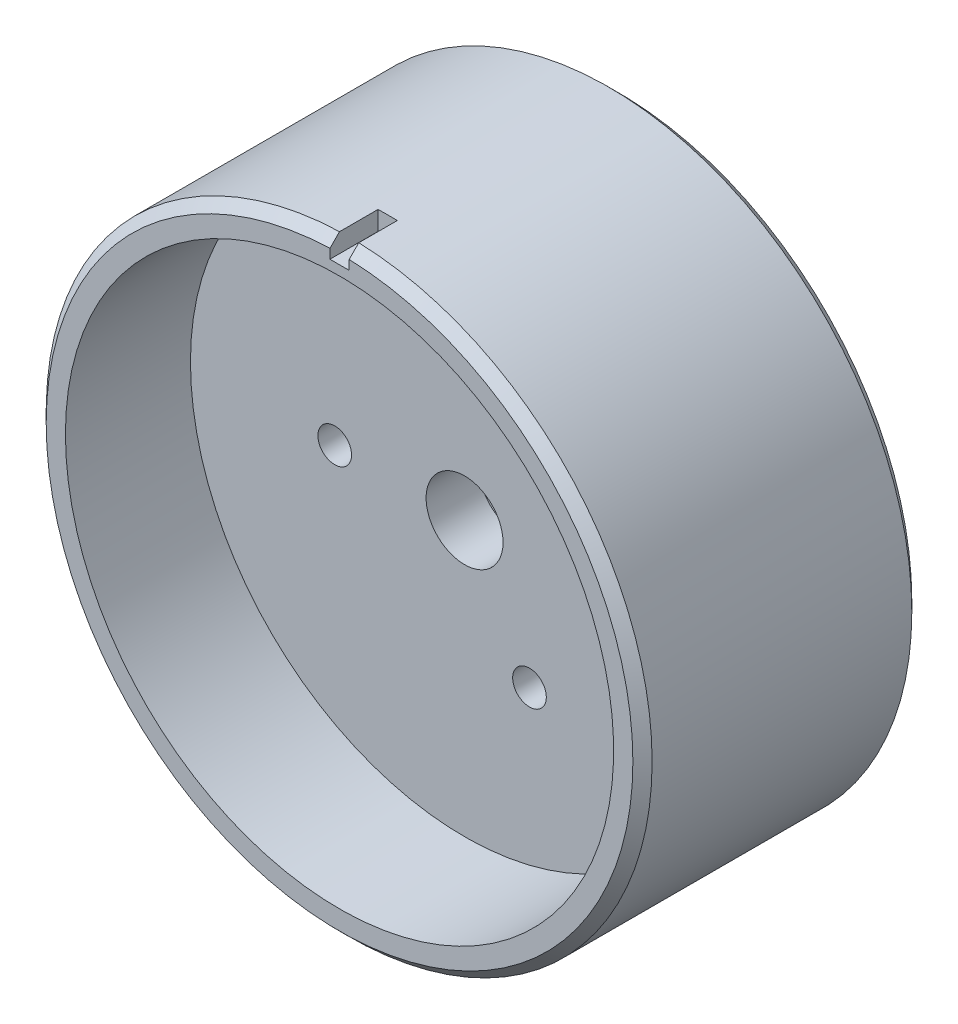
SolidWorks part; units mm, degrees
note: The reader was unsure of these and kept them because the rebuilt part matched: thickness of "Базовая кромка1", "Листовой металл4", "Листовой металл5", "Листовой металл6", "Листовой металл9", "Листовой металл10", "Листовой металл12", "Листовой металл13", "Листовой металл14", "Листовой металл15", "Листовой металл16", "Листовой металл17", "Листовой металл18".
material "PETG"
ref_plane "Спереди" through (0, 0, 0) normal (0, 0, 1) x (1, 0, 0)
ref_plane "Сверху" through (0, 0, 0) normal (0, 1, 0) x (1, 0, 0)
ref_plane "Справа" through (0, 0, 0) normal (1, 0, 0) x (0, 0, -1)
sketch "Эскиз1" plane through (0, 0, 0) normal (0, 0, 1) x (1, 0, 0)
  line L0 (0, 0) -> (-10.2, 0) construction
  line L1 (0, 0) -> (5.1, 8.8335) construction
  line L2 (0, 0) -> (5.1, -8.8335) construction
  line L3 (0, 0) -> (-25, 0) construction
  line L5 (0, 0) -> (0, 25) construction
  circle A0 centre (0, 0) radius 31.5
  circle A1 centre (0, 0) radius 25 construction
  circle A2 centre (0, 0) radius 13.5 construction
  circle A3 centre (-13.5, 0) radius 1.75
  circle A4 centre (6.75, 11.6913) radius 1.75
  circle A5 centre (6.75, -11.6913) radius 1.75
  circle A9 centre (0, 0) radius 10.2 construction
  point P19 (0, 0)
  point P24 (0, 0)
  dimension "D1" = 63
  dimension "D2" = 50
  dimension "D3" = 27
  dimension "D4" = 3.5
  dimension "D6" = 20.4
  dimension "D5" = 3
  dimension "D7" = 3
base flange "Базовая кромка1" sketch "Эскиз1" thickness 16 reverse thickness direction no parameters "D1"=2
chamfer "Фаска1" distance 1 angle 45 1 edges at (31.5, 0, -16)
sketch "Эскиз12" plane through (0, 0, -16) normal (0, 0, -1) x (-1, 0, 0)
  circle A0 centre (0, 0) radius 15.75
  dimension "D1" = 31.5
extrude "Вырез-Вытянуть2" cut sketch "Эскиз12" against normal blind 6
hole_wizard "Отверстие1" positions "Трехмерный эскиз2" profile "Эскиз8" legacy
sketch3d "Трехмерный эскиз2"
  point P9 (0, 0, 0)
sketch "Эскиз8" plane through (0, 0, 0) normal (1, 0, 0) x (0, -1, 0)
  line L0 (0, 0) -> (0, 5.5)
  line L1 (0, 5.5) -> (4, 5.5)
  line L2 (4, 5.5) -> (4, 0)
  line L3 (4, 0) -> (0, 0)
  line L4 (0, 110) -> (0, -10) construction
  dimension "Диаметр" = 8
  dimension "Глубина" = 5.5
chamfer "Фаска2" distance 0.5 angle 45 1 edges at (-15.75, 0, -16)
hole_wizard "Отверстия под штифты Ø6.0 мм1" positions "Трехмерный эскиз3" profile "Эскиз9" hole size "Ø6.0" standard "DIN"
sketch3d "Трехмерный эскиз3"
  point P0 (0, 25, -16)
sketch "Эскиз9" plane through (0, 25, -16) normal (1, 0, 0) x (0, 1, 0)
  line L0 (0, 0) -> (0, 7.8026)
  line L1 (0, 7.8026) -> (3, 6)
  line L2 (3, 6) -> (3, 0)
  line L5 (3, 0) -> (0, 0)
  line L10 (0, 7.8026) -> (-3, 6) construction
  line L11 (0, -6.35) -> (0, 107.95) construction
  dimension "Диаметр отверстия" = 6
  dimension "Глубина отверстия" = 6
  dimension "Угол заточки сверла" = 118
sketch "Эскиз11" plane through (0, 0, -10) normal (0, 0, -1) x (-1, 0, 0)
  circle A0 centre (13.5, 0) radius 3.25
  circle A1 centre (-6.75, -11.6913) radius 3.25
  circle A2 centre (-6.75, 11.6913) radius 3.25
  circle A6 centre (0, 0) radius 16.75 construction
  point P15 (0, 0)
  dimension "D1" = 6.5
  dimension "D3" = 33.5
  dimension "D2" = 3
extrude "Вырез-Вытянуть1" cut sketch "Эскиз11" against normal blind 4 and the other way up to next
sketch "Эскиз14" plane through (0, 0, -16) normal (0, 0, -1) x (-1, 0, 0)
  line L0 (-17.6777, 17.6777) -> (0, 0) construction
  line L1 (0, 0) -> (0, 25) construction
  circle A0 centre (0, 0) radius 25 construction
  point P0 (-17.6777, 17.6777)
  point P11 (17.6777, 17.6777)
  point P12 (17.6777, -17.6777)
  point P13 (-17.6777, -17.6777)
  point P14 (0, 0)
  dimension "D1" = 45
  dimension "D2" = 4
sketch "Эскиз10" plane through (-35.5333, 12.7174, -16) normal (0, 0, -1) x (-1, 0, 0)
  line L0 (-53.211, 4.9603) -> (-53.211, 11.5145) construction
  circle A0 centre (-53.211, 4.9603) radius 2.65
  dimension "D1" = 5.3
extrude "Вырез-Вытянуть41" cut sketch "Эскиз10" against normal blind 8
sketch "Эскиз111" plane through (-29.3081, 9.7444, -16) normal (0, 0, -1) x (-1, 0, 0)
  circle A1 centre (-46.9857, 7.9333) radius 2.65
  circle A2 centre (-46.9857, 7.9333) radius 2.65
  dimension "D1" = 0
curve "Спираль3" pitch 1 height 10 turns 10
ref_plane "Плоскость3" through (17.6777, 17.6777, -16) normal (0, 1, 0) x (1, 0, 0)
sketch "Эскиз121" plane through (17.6777, 17.6777, -16) normal (0, 1, 0) x (-1, 0, 0)
  line L0 (2.65, 0.45) -> (2.65, -0.45)
  line L1 (2.65, -0.45) -> (3.35, -0.0459)
  line L2 (3.35, -0.0459) -> (3.35, 0.0459)
  line L3 (3.35, 0.0459) -> (2.65, 0.45)
  point P2 (2.65, 0)
  dimension "D1" = 60
  dimension "D2" = 0.9
  dimension "D3" = 0.7
sweep "Вырез-По траектории3" cut profiles "Эскиз121" path "Спираль3"
pattern_circular "Круговой массив1" count 4 over 360 about axis through (0, 0, -16) along (0, 0, 1) of "Вырез-По траектории3", "Вырез-Вытянуть41"
ref_plane "Плоскость4" through (0, 0, -8.5) normal (0, 0, -1) x (-1, 0, 0)
sketch "Эскиз123" plane through (0, 0, -8.5) normal (0, 0, -1) x (-1, 0, 0)
  line L0 (0, 0) -> (39.4564, -4.3909) construction
  line L1 (0, 0) -> (28.2684, 0) construction
  line L2 (22.8589, -2.5438) -> (22.6322, -4.5813)
  line L3 (22.6322, -4.5813) -> (31.5769, -5.5767)
  line L5 (31.5769, -5.5767) -> (31.8037, -3.5393)
  line L6 (31.8037, -3.5393) -> (22.8589, -2.5438)
  dimension "D1" = 6.35
  dimension "D2" = 32
  dimension "D3" = 9
  dimension "D4" = 4.1
revolve "Вырез-Повернуть1" cut sketch "Эскиз123" angle 360 about L0
pattern_circular "Круговой массив2" count 2 every 24 about axis through (0, 0, -16) along (0, 0, 1) of "Вырез-Повернуть1"
sketch "Эскиз125" plane through (0, 0, 0) normal (0, 0, 1) x (1, 0, 0)
  circle A0 centre (0, 0) radius 28.5
  circle A1 centre (0, 0) radius 31.5
  circle A2 centre (0, 0) radius 31.5
  dimension "D2" = 57
  dimension "D1" = 0
extrude "Бобышка-Вытянуть1" add sketch "Эскиз125" along normal blind 13
sketch "Эскиз124" plane through (0, 0, 0) normal (0, 1, 0) x (1, 0, 0)
  line L0 (0, 15) -> (0, -13) construction
  line L1 (1, -8) -> (-1, -8)
  line L2 (1, -8) -> (1, -13)
  line L3 (1, -13) -> (-1, -13)
  line L4 (-1, -8) -> (-1, -13)
  line L5 (1, -8) -> (-1, -13) construction
  line L6 (1, -13) -> (-1, -8) construction
  line L8 (-31.5, -13) -> (31.5, -13) construction
  point P0 (0, -10.5)
  dimension "D1" = 2
  dimension "D2" = 5
extrude "Вырез-Вытянуть42" cut sketch "Эскиз124" against normal blind 2 from offset 31.5
chamfer "Фаска3" distance 1 angle 45 1 edges at (0, -31.5, 13)
sketch "Сгиб-Линии1" [suppressed] plane through (0, 0, 0) normal (0, 1, 0) x (1, 0, 0)
sketch "Граничная рамка1" [suppressed] plane through (0, 0, 0) normal (0, 1, 0) x (1, 0, 0)
sheet metal parameters "Листовой металл4" thickness 16 parameters "D1"=2, "D7"=10
flat pattern "Развертка4" [suppressed]
sketch "Сгиб-Линии2" plane through (0, 0, 0) normal (0, 1, 0) x (1, 0, 0)
sketch "Граничная рамка2" [suppressed] plane through (0, 0, 0) normal (0, 1, 0) x (1, 0, 0)
sheet metal parameters "Листовой металл5" thickness 16 parameters "D1"=2, "D7"=10
flat pattern "Развертка4"
sketch "Сгиб-Линии2" plane through (0, 0, 0) normal (0, 1, 0) x (1, 0, 0)
sketch "Граничная рамка2" [suppressed] plane through (0, 0, 0) normal (0, 1, 0) x (1, 0, 0)
sheet metal parameters "Листовой металл6" thickness 16 parameters "D1"=2, "D7"=10
flat pattern "Развертка4"
sketch "Сгиб-Линии2" plane through (0, 0, 0) normal (0, 1, 0) x (1, 0, 0)
sketch "Граничная рамка2" [suppressed] plane through (0, 0, 0) normal (0, 1, 0) x (1, 0, 0)
sheet metal parameters "Листовой металл9" thickness 16 parameters "D1"=2, "D7"=10
flat pattern "Развертка4"
sketch "Сгиб-Линии2" plane through (0, 0, 0) normal (0, 1, 0) x (1, 0, 0)
sketch3d "Граничная рамка2" [suppressed]
  line L0 (-31.5, 31.5, 0) -> (-31.5, -31.5, 0) construction
  line L1 (31.5, 31.5, 0) -> (31.5, -31.5, 0) construction
  line L2 (-31.5, 31.5, 0) -> (31.5, 31.5, 0) construction
  line L3 (-31.5, -31.5, 0) -> (31.5, -31.5, 0) construction
sheet metal parameters "Листовой металл10" thickness 16 parameters "D1"=2, "D7"=10
flat pattern "Развертка4"
sketch "Сгиб-Линии2" plane through (0, 0, 0) normal (0, 1, 0) x (1, 0, 0)
sketch3d "Граничная рамка2" [suppressed]
  line L0 (-31.5, 31.5, 0) -> (-31.5, -31.5, 0) construction
  line L1 (31.5, 31.5, 0) -> (31.5, -31.5, 0) construction
  line L2 (-31.5, 31.5, 0) -> (31.5, 31.5, 0) construction
  line L3 (-31.5, -31.5, 0) -> (31.5, -31.5, 0) construction
sheet metal parameters "Листовой металл12" thickness 16 parameters "D1"=2, "D7"=10
flat pattern "Развертка4"
sketch "Сгиб-Линии2" plane through (0, 0, 0) normal (0, 1, 0) x (1, 0, 0)
sketch3d "Граничная рамка2" [suppressed]
  line L0 (-31.5, -31.5, 0) -> (31.5, -31.5, 0) construction
  line L1 (-31.5, 31.5, 0) -> (31.5, 31.5, 0) construction
  line L2 (-31.5, -31.5, 0) -> (-31.5, 31.5, 0) construction
  line L3 (31.5, -31.5, 0) -> (31.5, 31.5, 0) construction
sheet metal parameters "Листовой металл13" thickness 16 parameters "D1"=2, "D7"=10
flat pattern "Развертка4"
sketch "Сгиб-Линии2" plane through (0, 0, 0) normal (0, 1, 0) x (1, 0, 0)
sketch3d "Граничная рамка2" [suppressed]
  line L0 (-31.5, -31.5, 0) -> (31.5, -31.5, 0) construction
  line L1 (-31.5, 31.5, 0) -> (31.5, 31.5, 0) construction
  line L2 (-31.5, -31.5, 0) -> (-31.5, 31.5, 0) construction
  line L3 (31.5, -31.5, 0) -> (31.5, 31.5, 0) construction
sheet metal parameters "Листовой металл14" thickness 16 parameters "D1"=2, "D7"=10
flat pattern "Развертка4"
sketch "Сгиб-Линии2" plane through (0, 0, 0) normal (0, 1, 0) x (1, 0, 0)
sketch3d "Граничная рамка2" [suppressed]
  line L0 (-31.5, -31.5, 0) -> (31.5, -31.5, 0) construction
  line L1 (-31.5, 31.5, 0) -> (31.5, 31.5, 0) construction
  line L2 (-31.5, -31.5, 0) -> (-31.5, 31.5, 0) construction
  line L3 (31.5, -31.5, 0) -> (31.5, 31.5, 0) construction
sheet metal parameters "Листовой металл15" thickness 16 parameters "D1"=2, "D7"=10
flat pattern "Развертка4"
sketch "Сгиб-Линии2" plane through (0, 0, 0) normal (0, 1, 0) x (1, 0, 0)
sketch3d "Граничная рамка2" [suppressed]
  line L0 (-31.5, -31.5, 0) -> (31.5, -31.5, 0) construction
  line L1 (-31.5, 31.5, 0) -> (31.5, 31.5, 0) construction
  line L2 (-31.5, -31.5, 0) -> (-31.5, 31.5, 0) construction
  line L3 (31.5, -31.5, 0) -> (31.5, 31.5, 0) construction
sheet metal parameters "Листовой металл16" thickness 16 parameters "D1"=2, "D7"=10
flat pattern "Развертка4"
sketch "Сгиб-Линии2" plane through (0, 0, 0) normal (0, 1, 0) x (1, 0, 0)
sketch3d "Граничная рамка2" [suppressed]
  line L0 (-31.5, -31.5, 0) -> (31.5, -31.5, 0) construction
  line L1 (-31.5, 31.5, 0) -> (31.5, 31.5, 0) construction
  line L2 (-31.5, -31.5, 0) -> (-31.5, 31.5, 0) construction
  line L3 (31.5, -31.5, 0) -> (31.5, 31.5, 0) construction
sheet metal parameters "Листовой металл17" thickness 16 parameters "D1"=2, "D7"=10
flat pattern "Развертка4"
sketch "Сгиб-Линии2" plane through (0, 0, 0) normal (0, 1, 0) x (1, 0, 0)
sketch3d "Граничная рамка2" [suppressed]
  line L0 (-31.5, -31.5, 0) -> (31.5, -31.5, 0) construction
  line L1 (-31.5, 31.5, 0) -> (31.5, 31.5, 0) construction
  line L2 (-31.5, -31.5, 0) -> (-31.5, 31.5, 0) construction
  line L3 (31.5, -31.5, 0) -> (31.5, 31.5, 0) construction
sheet metal parameters "Листовой металл18" thickness 16 parameters "D1"=2, "D7"=10
flat pattern "Развертка4"
sketch "Сгиб-Линии2" plane through (0, 0, 0) normal (0, 1, 0) x (1, 0, 0)
sketch3d "Граничная рамка2" [suppressed]
  line L0 (-31.5, -31.5, 0) -> (31.5, -31.5, 0) construction
  line L1 (-31.5, 31.5, 0) -> (31.5, 31.5, 0) construction
  line L2 (-31.5, -31.5, 0) -> (-31.5, 31.5, 0) construction
  line L3 (31.5, -31.5, 0) -> (31.5, 31.5, 0) construction
